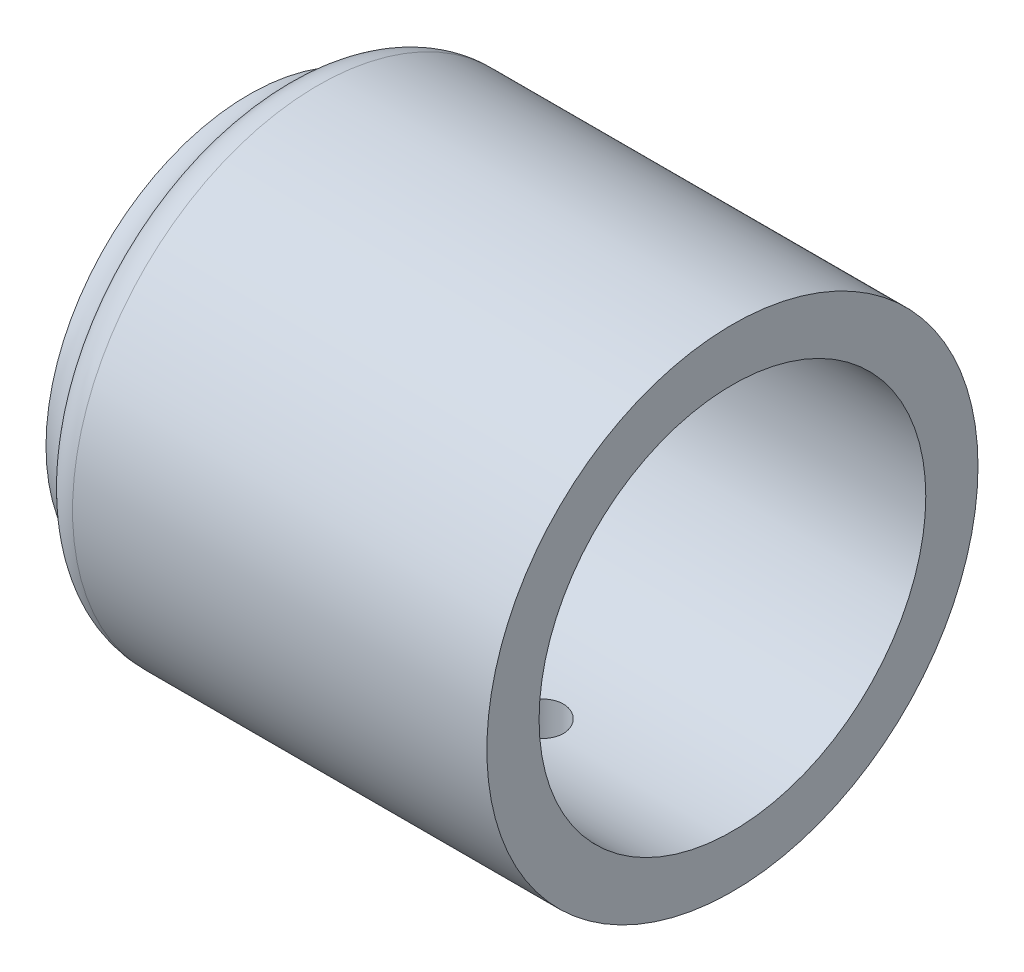
SolidWorks part; units mm, degrees
material "6061 Alloy"
ref_plane "Front Plane" through (0, 0, 0) normal (0, 0, 1) x (1, 0, 0)
ref_plane "Top Plane" through (0, 0, 0) normal (0, 1, 0) x (1, 0, 0)
ref_plane "Right Plane" through (0, 0, 0) normal (1, 0, 0) x (0, 0, -1)
sketch "Sketch1" plane through (0, 0, 0) normal (1, 0, 0) x (0, 0, -1)
  circle A0 centre (0, 0) radius 20
  circle A1 centre (0, 0) radius 25.4
  dimension "D1" = 40
  dimension "D2" = 50.8
extrude "Boss-Extrude1" add sketch "Sketch1" along normal blind 50
sketch "Sketch2" plane through (0, 0, 0) normal (-1, 0, 0) x (0, 0, 1)
  circle A0 centre (0, 0) radius 30
  circle A1 centre (0, 0) radius 21
  dimension "D1" = 42
  dimension "D2" = 60
extrude "Cut-Extrude1" cut sketch "Sketch2" against normal blind 4
fillet "Fillet1" radius 4 1 edges at (4, 0, 21)
ref_plane "Plane1" through (4, 0, 0) normal (-1, 0, 0) x (0, 0, 1)
fillet "Fillet2" radius 4 1 edges at (4, 0, 25.4)
ref_plane "Plane2" through (0, -25.4, 0) normal (0, -1, 0) x (-1, 0, 0)
hole_wizard "M6x1.0 Tapped Hole1" positions "Sketch4" profile "Sketch5" tap size "M6x1.0" standard "ANSI Metric"
sketch "Sketch4" plane through (0, -25.4, 0) normal (0, -1, 0) x (-1, 0, 0)
  line L0 (-27.5, 0) -> (27.5, 0) construction
  line L1 (-50, 25.4) -> (-50, -25.4) construction
  point P0 (-30, 0)
  dimension "D1" = 20
sketch "Sketch5" plane through (30, -25.4, 0) normal (1, 0, 0) x (0, 0, -1)
  line L0 (0, 0) -> (0, 15)
  line L1 (0, 15) -> (2.5, 13.4978)
  line L2 (2.5, 13.4978) -> (2.5, 0)
  line L5 (2.5, 0) -> (0, 0)
  line L10 (0, 15) -> (-2.5, 13.4978) construction
  line L11 (0, -6.35) -> (0, 107.95) construction
  dimension "Tap Drill Dia." = 5
  dimension "Tap Drill Depth" = 15
  dimension "Drill Angle" = 118
cosmetic thread "Hole Thread1" parameters "D1"=5.5569, "D2"=6
